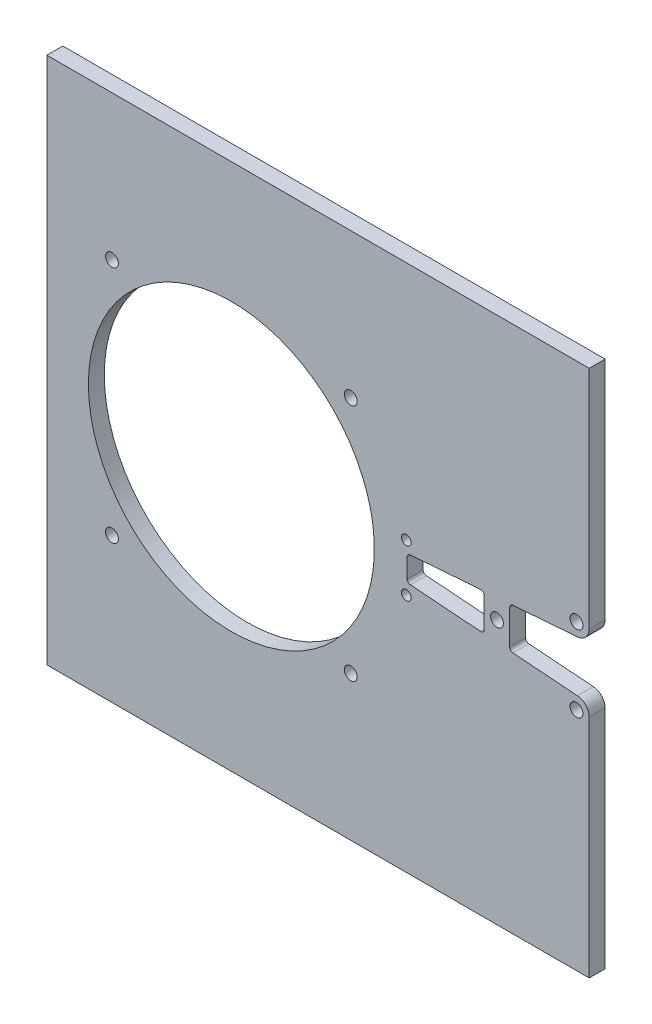
SolidWorks part; units mm, degrees
material "Thornel Mat VMA"
ref_plane "前视基准面" through (0, 0, 0) normal (0, 0, 1) x (1, 0, 0)
ref_plane "上视基准面" through (0, 0, 0) normal (0, 1, 0) x (1, 0, 0)
ref_plane "右视基准面" through (0, 0, 0) normal (1, 0, 0) x (0, 0, -1)
other "Configuration Table"
sketch "草图1" plane through (0, 0, 0) normal (0, 0, 1) x (1, 0, 0)
  line L1 (-100, -83) -> (100, -83)
  line L2 (-100, -83) -> (-100, 83)
  line L3 (-100, 83) -> (100, 83)
  line L4 (100, -83) -> (100, 83)
  line L5 (-100, -83) -> (100, 83) construction
  line L6 (-100, 83) -> (100, -83) construction
  point P0 (0, 0)
  dimension "D1" = 200
  dimension "D2" = 166
extrude "凸台-拉伸1" add sketch "草图1" along normal blind 5
sketch "草图2" plane through (0, 0, 5) normal (0, 0, 1) x (1, 0, 0)
  circle A0 centre (-42, 0) radius 44.75 construction
  circle A1 centre (-42, 0) radius 44.75
extrude "切除-拉伸1" cut sketch "草图2" against normal blind 44
sketch "草图3" plane through (0, 0, 5) normal (0, 0, 1) x (1, 0, 0)
  circle A0 centre (-79.54, -37.5) radius 2.15 construction
  circle A1 centre (-79.54, 37.5) radius 2.15 construction
  circle A2 centre (-4.46, -37.5) radius 2.15 construction
  circle A3 centre (-4.46, 37.5) radius 2.15 construction
  circle A4 centre (-79.54, -37.5) radius 2.15 construction
  circle A5 centre (-79.54, 37.5) radius 2.15 construction
  circle A6 centre (-4.46, -37.5) radius 2.15 construction
  circle A7 centre (-4.46, 37.5) radius 2.15 construction
  circle A8 centre (-79.54, -37.5) radius 2.025
  circle A9 centre (-4.46, -37.5) radius 2.025
  circle A10 centre (-4.46, 37.5) radius 2.025
  circle A11 centre (-79.54, 37.5) radius 2.025
  dimension "D1" = 4.05
extrude "切除-拉伸2" cut sketch "草图3" against normal blind 44
other "移动面1" flip direction yes face at (-86.75, 0, 0) offset 0.2 parameters "D1"=0.2
sketch "草图4" plane through (0, 0, 5) normal (0, 0, 1) x (1, 0, 0)
  circle A0 centre (66.5, 12) radius 1.65 construction
  circle A1 centre (66.5, -12) radius 1.65 construction
  circle A2 centre (13, 7.5) radius 1.25 construction
  circle A3 centre (13, -7.5) radius 1.25 construction
  circle A4 centre (66.5, 12) radius 1.65 construction
  circle A5 centre (66.5, -12) radius 1.65 construction
  circle A6 centre (13, 7.5) radius 1.25 construction
  circle A7 centre (13, -7.5) radius 1.25 construction
  circle A8 centre (13, 7.5) radius 1.525
  circle A9 centre (13, -7.5) radius 1.525
  circle A10 centre (66.5, 12) radius 2.025
  circle A11 centre (66.5, -12) radius 2.025
  dimension "D1" = 4.05
  dimension "D2" = 3.05
extrude "切除-拉伸3" cut sketch "草图4" against normal blind 44
sketch "草图5" plane through (0, 0, 0) normal (0, 0, -1) x (-1, 0, 0)
  line L0 (-70.5, 12) -> (-70.5, -12) construction
  line L1 (-70.5, 83) -> (-70.5, -83)
  line L2 (-100, 83) -> (100, 83) construction
  line L3 (100, -83) -> (-100, -83) construction
  line L4 (-70.5, -83) -> (-100, -83)
  line L5 (-100, -83) -> (-100, 83)
  line L6 (-100, 83) -> (-70.5, 83)
extrude "切除-拉伸4" cut sketch "草图5" against normal blind 44
sketch "草图6" plane through (0, 0, 0) normal (0, 0, -1) x (-1, 0, 0)
  line L0 (-70.5, -83) -> (-70.5, 83) construction
  line L1 (-66.8, -8.0113) -> (-13.2644, -3.9849)
  line L2 (-66.8, 8.0113) -> (-13.2644, 3.9849)
  line L3 (-13.2644, 3.9849) -> (-13.2644, -3.9849)
  line L4 (-70.5, 12) -> (-70.5, -12)
  circle A0 centre (-66.5, 12) radius 4
  circle A1 centre (-66.5, -12) radius 4
  circle A3 centre (-13, 7.5) radius 3.525
  circle A4 centre (-13, -7.5) radius 3.525
  circle A5 centre (-13, 7.5) radius 1.525 construction
  point P22 (-13.3344, 3.9909)
  point P23 (-13, -3.2229)
  point P24 (0, 0)
  line M5 (-70.5, 83) -> (-70.5, -83)
  dimension "D1" = 2
extrude "切除-拉伸5" cut sketch "草图6" against normal blind 44 contours A4 L3 L2 A0 A1 L1 M5 region at (45.4262, 0, 0)
sketch "草图7" plane through (0, 0, 5) normal (0, 0, 1) x (1, 0, 0)
  line L0 (37.5, 5.8077) -> (37.5, -5.8077)
  line L1 (66.8, 8.0113) -> (13.2644, 3.9849) construction
  line L2 (66.8, -8.0113) -> (13.2644, -3.9849) construction
  line L3 (45.5, 6.4093) -> (45.5, -6.4093)
  line L4 (37.5, -5.8077) -> (45.5, -6.4093)
  line L5 (37.5, 5.8077) -> (45.5, 6.4093)
  circle A0 centre (41.5, 0) radius 1.65 construction
  circle A1 centre (41.5, 0) radius 1.65 construction
  circle A2 centre (41.5, 0) radius 2.025
  dimension "D3" = 4.05
  dimension "D1" = 4
  dimension "D2" = 4
extrude "凸台-拉伸2" add sketch "草图7" against normal up to surface (5 mm away) up to face at (64.475, -12, 0)
fillet "圆角1" radius 1.1 6 edges at (13.2644, -3.9849, 2.5) (13.2644, 3.9849, 2.5) (37.5, 5.8077, 2.5) (37.5, -5.8077, 2.5) (45.5, -6.4093, 2.5) (45.5, 6.4093, 2.5)
